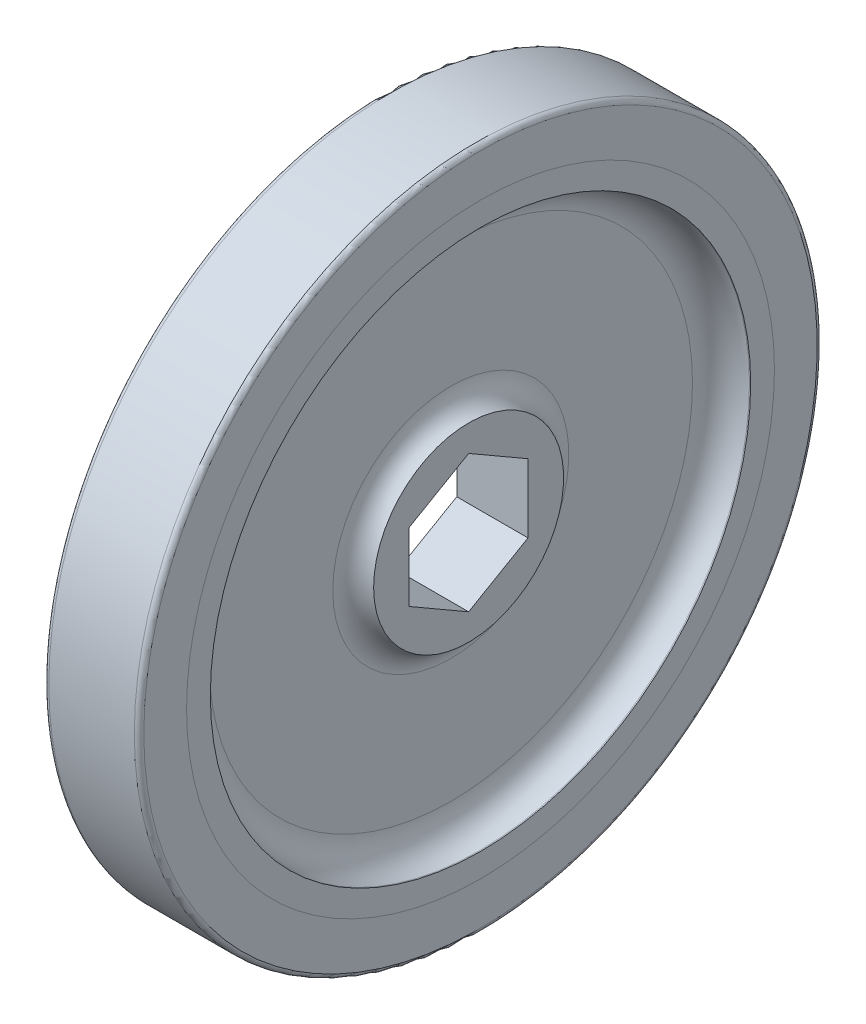
SolidWorks part; units mm, degrees
material "ABS"
ref_plane "Plan de face" through (0, 0, 0) normal (0, 0, 1) x (1, 0, 0)
ref_plane "Plan de dessus" through (0, 0, 0) normal (0, 1, 0) x (1, 0, 0)
ref_plane "Plan de droite" through (0, 0, 0) normal (1, 0, 0) x (0, 0, -1)
sketch "Esquisse1" plane through (0, 0, 0) normal (0, 0, 1) x (1, 0, 0)
  line L0 (0, 0) -> (0, 10.16) construction
  line L1 (1.905, 10.16) -> (3.81, 10.16)
  line L2 (-3.81, 10.16) -> (-3.81, 0)
  line L3 (-3.81, 0) -> (3.81, 0)
  line L4 (3.81, 10.16) -> (3.81, 0)
  line L5 (-1.905, 28.8925) -> (1.905, 28.8925) construction
  line L6 (-1.905, 28.8925) -> (-1.905, 10.16)
  line L7 (-1.905, 10.16) -> (1.905, 10.16) construction
  line L8 (1.905, 28.8925) -> (1.905, 10.16)
  line L9 (-1.905, 10.16) -> (-3.81, 10.16)
  line L10 (-5.08, 28.8925) -> (-1.905, 28.8925)
  line L11 (0, 31.4325) -> (0, 28.8925) construction
  line L12 (-5.08, 31.4325) -> (-5.08, 28.8925)
  line L13 (1.905, 28.8925) -> (5.08, 28.8925)
  line L14 (5.08, 31.4325) -> (5.08, 28.8925)
  line L15 (-2.54, 33.9725) -> (2.54, 33.9725)
  line L16 (-2.54, 33.9725) -> (-2.54, 31.4325)
  line L17 (-2.54, 31.4325) -> (2.54, 31.4325) construction
  line L18 (2.54, 33.9725) -> (2.54, 31.4325)
  line L19 (2.54, 31.4325) -> (5.08, 31.4325)
  line L20 (-2.54, 31.4325) -> (-5.08, 31.4325)
  dimension "D1" = 7.62
  dimension "D2" = 10.16
  dimension "D3" = 3.81
  dimension "D4" = 28.8925
  dimension "D5" = 31.4325
  dimension "D6" = 10.16
  dimension "D7" = 5.08
  dimension "D8" = 33.9725
revolve "Révolution1" add sketch "Esquisse1" angle 360 about L3
fillet "Congé1" radius 2.54 2 edges at (-1.905, 0, 10.16) (1.905, 0, 10.16)
fillet "Congé2" radius 3.048 2 edges at (1.905, 0, 28.8925) (-1.905, 0, 28.8925)
sketch "Esquisse3" plane through (0, 0, 0) normal (1, 0, 0) x (0, 0, -1)
  line L1 (0, 7.3323) -> (-6.35, 3.6662)
  line L2 (-6.35, 3.6662) -> (-6.35, -3.6662)
  line L3 (-6.35, -3.6662) -> (0, -7.3323)
  line L4 (0, -7.3323) -> (6.35, -3.6662)
  line L5 (6.35, -3.6662) -> (6.35, 3.6662)
  line L6 (6.35, 3.6662) -> (0, 7.3323)
  circle A0 centre (0, 0) radius 6.35 construction
  dimension "D1" = 12.7
extrude "hex_hole" cut sketch "Esquisse3" against normal through all and the other way through all
sketch "Esquisse2" plane through (0, 0, 0) normal (0, 0, 1) x (1, 0, 0)
  line L0 (-5.08, 31.4325) -> (-2.54, 31.4325)
  line L1 (-2.54, 31.4325) -> (-2.54, 33.9725)
  line L2 (-2.54, 33.9725) -> (2.54, 33.9725)
  line L3 (2.54, 33.9725) -> (2.54, 31.4325)
  line L4 (2.54, 31.4325) -> (5.08, 31.4325)
  line L5 (5.08, 31.4325) -> (5.08, 36.5125)
  line L6 (5.08, 36.5125) -> (-5.08, 36.5125)
  line L7 (-5.08, 36.5125) -> (-5.08, 31.4325)
  line L8 (-3.81, 0) -> (3.81, 0) construction
  dimension "D1" = 36.5125
revolve "Révolution2" add sketch "Esquisse2" angle 360 about L8
fillet "Congé3" radius 0.508 2 edges at (-5.08, 0, 36.5125) (5.08, 0, 36.5125)
